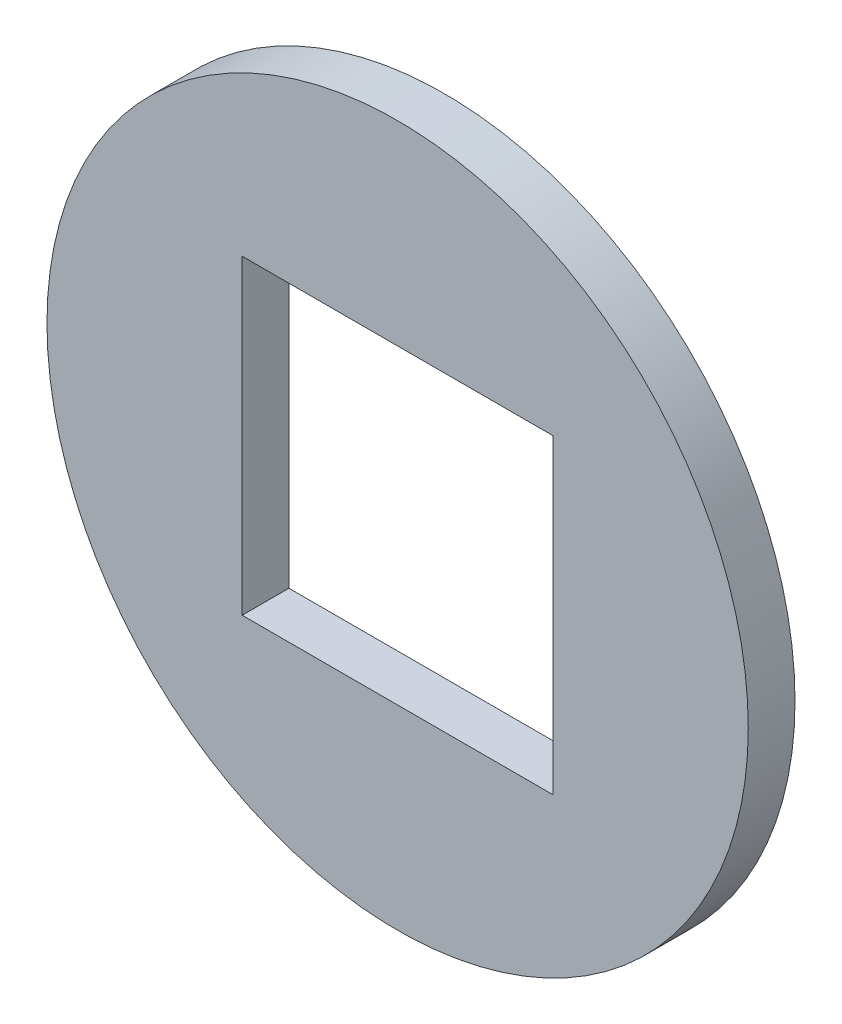
SolidWorks part; units mm, degrees
ref_plane "Front Plane" through (0, 0, 0) normal (0, 0, 1) x (1, 0, 0)
ref_plane "Top Plane" through (0, 0, 0) normal (0, 1, 0) x (1, 0, 0)
ref_plane "Right Plane" through (0, 0, 0) normal (1, 0, 0) x (0, 0, -1)
sketch "Sketch1" plane through (0, 0, 0) normal (0, 0, 1) x (1, 0, 0)
  line L1 (-3.325, -3.325) -> (3.325, -3.325)
  line L2 (-3.325, -3.325) -> (-3.325, 3.325)
  line L3 (-3.325, 3.325) -> (3.325, 3.325)
  line L4 (3.325, -3.325) -> (3.325, 3.325)
  line L5 (-3.325, -3.325) -> (3.325, 3.325) construction
  line L6 (-3.325, 3.325) -> (3.325, -3.325) construction
  circle A0 centre (0, 0) radius 7.5
  point P0 (0, 0)
  point P9 (0, 0)
  dimension "D2" = 15
  dimension "D1" = 6.65
extrude "Boss-Extrude1" add sketch "Sketch1" along normal mid plane 1
ref_axis "Axis1" through (0, 0, 0) along (0, 0, 1)
